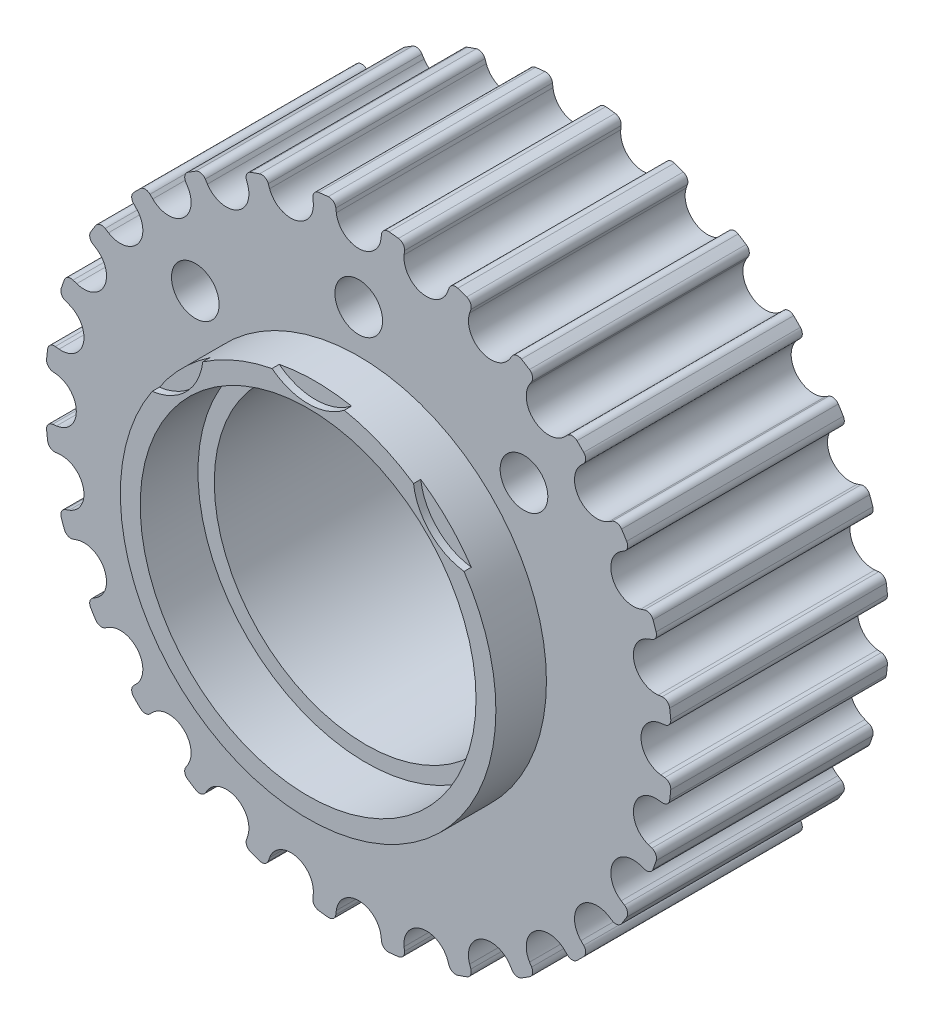
SolidWorks part; units mm, degrees
note: The reader was unsure of these and kept them because the rebuilt part matched: shared geometry of "草图15<2>".
ref_plane "前视基准面" through (0, 0, 0) normal (0, 0, 1) x (1, 0, 0)
ref_plane "上视基准面" through (0, 0, 0) normal (0, 1, 0) x (1, 0, 0)
ref_plane "右视基准面" through (0, 0, 0) normal (1, 0, 0) x (0, 0, -1)
sketch "草图2" plane through (0, 0, 0) normal (0, 0, 1) x (1, 0, 0)
  line L36 (1.3319, 20.7804) -> (1.2989, 20.5118)
  line L37 (-1.7978, 20.5118) -> (-1.8308, 20.7804)
  line L38 (-3.4222, 20.6011) -> (-3.3946, 20.3319)
  line L39 (-6.4137, 19.6428) -> (-6.5056, 19.8973)
  line L40 (-8.0172, 19.3684) -> (-7.9303, 19.1121)
  line L41 (-10.7204, 17.7684) -> (-10.8667, 17.9962)
  line L42 (-12.2227, 17.1441) -> (-12.081, 16.9135)
  line L43 (-14.5021, 14.9827) -> (-14.6954, 15.1722)
  line L44 (-15.8278, 14.0398) -> (-15.6383, 13.8465)
  line L45 (-17.5691, 11.4254) -> (-17.7997, 11.5671)
  line L46 (-18.6517, 10.2111) -> (-18.424, 10.0648)
  line L47 (-19.7676, 7.2748) -> (-20.024, 7.3616)
  line L48 (-20.5529, 5.85) -> (-20.2983, 5.7581)
  line L49 (-20.9874, 2.739) -> (-21.2567, 2.7666)
  line L50 (-21.436, 1.1752) -> (-21.1673, 1.1423)
  line L51 (-21.1673, -1.9545) -> (-21.436, -1.9875)
  line L52 (-21.2567, -3.5789) -> (-20.9874, -3.5512)
  line L53 (-20.2983, -6.5703) -> (-20.5529, -6.6623)
  line L54 (-20.024, -8.1739) -> (-19.7676, -8.087)
  line L55 (-18.424, -10.8771) -> (-18.6517, -11.0234)
  line L56 (-17.7997, -12.3793) -> (-17.5691, -12.2376)
  line L57 (-15.6383, -14.6588) -> (-15.8278, -14.8521)
  line L58 (-14.6954, -15.9845) -> (-14.5021, -15.795)
  line L59 (-12.081, -17.7258) -> (-12.2227, -17.9564)
  line L60 (-10.8667, -18.8084) -> (-10.7204, -18.5807)
  line L61 (-7.9303, -19.9243) -> (-8.0172, -20.1806)
  line L62 (-6.5056, -20.7096) -> (-6.4137, -20.455)
  line L63 (-3.3946, -21.1441) -> (-3.4222, -21.4133)
  line L64 (-1.8308, -21.5926) -> (-1.7978, -21.324)
  line L65 (1.2989, -21.324) -> (1.3319, -21.5926)
  line L66 (2.9233, -21.4133) -> (2.8957, -21.1441)
  line L67 (5.9148, -20.455) -> (6.0067, -20.7096)
  line L68 (7.5183, -20.1806) -> (7.4314, -19.9243)
  line L69 (10.2215, -18.5807) -> (10.3678, -18.8084)
  line L70 (11.7238, -17.9564) -> (11.5821, -17.7258)
  line L71 (14.0032, -15.795) -> (14.1965, -15.9845)
  line L72 (15.3289, -14.8521) -> (15.1394, -14.6588)
  line L73 (17.0702, -12.2376) -> (17.3008, -12.3793)
  line L74 (18.1528, -11.0234) -> (17.9251, -10.8771)
  line L75 (19.2687, -8.087) -> (19.5251, -8.1739)
  line L76 (20.054, -6.6623) -> (19.7994, -6.5703)
  line L77 (20.4885, -3.5512) -> (20.7578, -3.5789)
  line L78 (20.9371, -1.9875) -> (20.6684, -1.9545)
  line L79 (20.6684, 1.1423) -> (20.9371, 1.1752)
  line L80 (20.7578, 2.7666) -> (20.4885, 2.739)
  line L81 (19.7994, 5.7581) -> (20.054, 5.85)
  line L82 (19.5251, 7.3616) -> (19.2687, 7.2748)
  line L83 (17.9251, 10.0648) -> (18.1528, 10.2111)
  line L84 (17.3008, 11.5671) -> (17.0702, 11.4254)
  line L85 (15.1394, 13.8465) -> (15.3289, 14.0398)
  line L86 (14.1965, 15.1722) -> (14.0032, 14.9827)
  line L87 (11.5821, 16.9135) -> (11.7238, 17.1441)
  line L88 (10.3678, 17.9962) -> (10.2215, 17.7684)
  line L89 (7.4314, 19.1121) -> (7.5183, 19.3684)
  line L90 (6.0067, 19.8973) -> (5.9148, 19.6428)
  line L91 (2.8957, 20.3319) -> (2.9233, 20.6011)
  circle A72 centre (-0.2458, -0.3677) radius 12 construction
  circle A73 centre (-0.2458, -0.3677) radius 10.5
  arc A74 (2.9233, 20.6011) -> (2.5067, 21.1262) centre (2.4458, 20.6501) ccw
  arc A75 (2.5067, 21.1262) -> (1.8549, 21.1996) centre (-0.2495, -0.4061) ccw
  arc A76 (1.8549, 21.1996) -> (1.3319, 20.7804) centre (1.8083, 20.7219) ccw
  arc A77 (-1.7978, 20.5118) -> (1.2989, 20.5118) centre (-0.2495, 20.7019) ccw
  arc A78 (-1.8308, 20.7804) -> (-2.3538, 21.1996) centre (-2.3072, 20.7219) ccw
  arc A79 (-2.3538, 21.1996) -> (-3.0056, 21.1262) centre (-0.2495, -0.4061) ccw
  arc A80 (-3.0056, 21.1262) -> (-3.4222, 20.6011) centre (-2.9447, 20.6501) ccw
  arc A81 (-6.4137, 19.6428) -> (-3.3946, 20.3319) centre (-4.9464, 20.1727) ccw
  arc A82 (-6.5056, 19.8973) -> (-7.1087, 20.1897) centre (-6.9571, 19.7343) ccw
  arc A83 (-7.1087, 20.1897) -> (-7.7279, 19.973) centre (-0.2495, -0.4061) ccw
  arc A84 (-7.7279, 19.973) -> (-8.0172, 19.3684) centre (-7.5626, 19.5224) ccw
  arc A85 (-10.7204, 17.7684) -> (-7.9303, 19.1121) centre (-9.4079, 18.6115) ccw
  arc A86 (-10.8667, 17.9962) -> (-11.5198, 18.147) centre (-11.2706, 17.7367) ccw
  arc A87 (-11.5198, 18.147) -> (-12.0752, 17.798) centre (-0.2495, -0.4061) ccw
  arc A88 (-12.0752, 17.798) -> (-12.2227, 17.1441) centre (-11.8137, 17.3954) ccw
  arc A89 (-14.5021, 14.9827) -> (-12.081, 16.9135) centre (-13.4101, 16.0968) ccw
  arc A90 (-14.6954, 15.1722) -> (-15.3656, 15.1739) centre (-15.0314, 14.8294) ccw
  arc A91 (-15.3656, 15.1739) -> (-15.8295, 14.7101) centre (-0.2495, -0.4061) ccw
  arc A92 (-15.8295, 14.7101) -> (-15.8278, 14.0398) centre (-15.485, 14.3758) ccw
  arc A93 (-17.5691, 11.4254) -> (-15.6383, 13.8465) centre (-16.7524, 12.7545) ccw
  arc A94 (-17.7997, 11.5671) -> (-18.4535, 11.4196) centre (-18.051, 11.1582) ccw
  arc A95 (-18.4535, 11.4196) -> (-18.8026, 10.8642) centre (-0.2495, -0.4061) ccw
  arc A96 (-18.8026, 10.8642) -> (-18.6517, 10.2111) centre (-18.3923, 10.615) ccw
  arc A97 (-19.7676, 7.2748) -> (-18.424, 10.0648) centre (-19.2671, 8.7523) ccw
  arc A98 (-20.024, 7.3616) -> (-20.6286, 7.0724) centre (-20.178, 6.907) ccw
  arc A99 (-20.6286, 7.0724) -> (-20.8453, 6.4532) centre (-0.2495, -0.4061) ccw
  arc A100 (-20.8453, 6.4532) -> (-20.5529, 5.85) centre (-20.3899, 6.3015) ccw
  arc A101 (-20.9874, 2.739) -> (-20.2983, 5.7581) centre (-20.8282, 4.2909) ccw
  arc A102 (-21.2567, 2.7666) -> (-21.7818, 2.3501) centre (-21.3057, 2.2891) ccw
  arc A103 (-21.7818, 2.3501) -> (-21.8552, 1.6982) centre (-0.2495, -0.4061) ccw
  arc A104 (-21.8552, 1.6982) -> (-21.436, 1.1752) centre (-21.3775, 1.6517) ccw
  arc A105 (-21.1673, -1.9545) -> (-21.1673, 1.1423) centre (-21.3575, -0.4061) ccw
  arc A106 (-21.436, -1.9875) -> (-21.8552, -2.5104) centre (-21.3775, -2.4639) ccw
  arc A107 (-21.8552, -2.5104) -> (-21.7818, -3.1623) centre (-0.2495, -0.4061) ccw
  arc A108 (-21.7818, -3.1623) -> (-21.2567, -3.5789) centre (-21.3057, -3.1014) ccw
  arc A109 (-20.2983, -6.5703) -> (-20.9874, -3.5512) centre (-20.8282, -5.1031) ccw
  arc A110 (-20.5529, -6.6623) -> (-20.8453, -7.2654) centre (-20.3899, -7.1137) ccw
  arc A111 (-20.8453, -7.2654) -> (-20.6286, -7.8846) centre (-0.2495, -0.4061) ccw
  arc A112 (-20.6286, -7.8846) -> (-20.024, -8.1739) centre (-20.178, -7.7192) ccw
  arc A113 (-18.424, -10.8771) -> (-19.7676, -8.087) centre (-19.2671, -9.5645) ccw
  arc A114 (-18.6517, -11.0234) -> (-18.8026, -11.6764) centre (-18.3923, -11.4272) ccw
  arc A115 (-18.8026, -11.6764) -> (-18.4535, -12.2319) centre (-0.2495, -0.4061) ccw
  arc A116 (-18.4535, -12.2319) -> (-17.7997, -12.3793) centre (-18.051, -11.9704) ccw
  arc A117 (-15.6383, -14.6588) -> (-17.5691, -12.2376) centre (-16.7524, -13.5667) ccw
  arc A118 (-15.8278, -14.8521) -> (-15.8295, -15.5223) centre (-15.485, -15.1881) ccw
  arc A119 (-15.8295, -15.5223) -> (-15.3656, -15.9862) centre (-0.2495, -0.4061) ccw
  arc A120 (-15.3656, -15.9862) -> (-14.6954, -15.9845) centre (-15.0314, -15.6417) ccw
  arc A121 (-12.081, -17.7258) -> (-14.5021, -15.795) centre (-13.4101, -16.909) ccw
  arc A122 (-12.2227, -17.9564) -> (-12.0752, -18.6102) centre (-11.8137, -18.2077) ccw
  arc A123 (-12.0752, -18.6102) -> (-11.5198, -18.9592) centre (-0.2495, -0.4061) ccw
  arc A124 (-11.5198, -18.9592) -> (-10.8667, -18.8084) centre (-11.2706, -18.549) ccw
  arc A125 (-7.9303, -19.9243) -> (-10.7204, -18.5807) centre (-9.4079, -19.4238) ccw
  arc A126 (-8.0172, -20.1806) -> (-7.7279, -20.7853) centre (-7.5626, -20.3347) ccw
  arc A127 (-7.7279, -20.7853) -> (-7.1087, -21.0019) centre (-0.2495, -0.4061) ccw
  arc A128 (-7.1087, -21.0019) -> (-6.5056, -20.7096) centre (-6.9571, -20.5465) ccw
  arc A129 (-3.3946, -21.1441) -> (-6.4137, -20.455) centre (-4.9464, -20.9849) ccw
  arc A130 (-3.4222, -21.4133) -> (-3.0056, -21.9384) centre (-2.9447, -21.4623) ccw
  arc A131 (-3.0056, -21.9384) -> (-2.3538, -22.0119) centre (-0.2495, -0.4061) ccw
  arc A132 (-2.3538, -22.0119) -> (-1.8308, -21.5926) centre (-2.3072, -21.5341) ccw
  arc A133 (1.2989, -21.324) -> (-1.7978, -21.324) centre (-0.2495, -21.5141) ccw
  arc A134 (1.3319, -21.5926) -> (1.8549, -22.0119) centre (1.8083, -21.5341) ccw
  arc A135 (1.8549, -22.0119) -> (2.5067, -21.9384) centre (-0.2495, -0.4061) ccw
  arc A136 (2.5067, -21.9384) -> (2.9233, -21.4133) centre (2.4458, -21.4623) ccw
  arc A137 (5.9148, -20.455) -> (2.8957, -21.1441) centre (4.4475, -20.9849) ccw
  arc A138 (6.0067, -20.7096) -> (6.6098, -21.0019) centre (6.4582, -20.5465) ccw
  arc A139 (6.6098, -21.0019) -> (7.229, -20.7853) centre (-0.2495, -0.4061) ccw
  arc A140 (7.229, -20.7853) -> (7.5183, -20.1806) centre (7.0637, -20.3347) ccw
  arc A141 (10.2215, -18.5807) -> (7.4314, -19.9243) centre (8.909, -19.4238) ccw
  arc A142 (10.3678, -18.8084) -> (11.0209, -18.9592) centre (10.7716, -18.549) ccw
  arc A143 (11.0209, -18.9592) -> (11.5763, -18.6102) centre (-0.2495, -0.4061) ccw
  arc A144 (11.5763, -18.6102) -> (11.7238, -17.9564) centre (11.3148, -18.2077) ccw
  arc A145 (14.0032, -15.795) -> (11.5821, -17.7258) centre (12.9112, -16.909) ccw
  arc A146 (14.1965, -15.9845) -> (14.8667, -15.9862) centre (14.5325, -15.6417) ccw
  arc A147 (14.8667, -15.9862) -> (15.3306, -15.5223) centre (-0.2495, -0.4061) ccw
  arc A148 (15.3306, -15.5223) -> (15.3289, -14.8521) centre (14.9861, -15.1881) ccw
  arc A149 (17.0702, -12.2376) -> (15.1394, -14.6588) centre (16.2534, -13.5667) ccw
  arc A150 (17.3008, -12.3793) -> (17.9546, -12.2319) centre (17.5521, -11.9704) ccw
  arc A151 (17.9546, -12.2319) -> (18.3036, -11.6764) centre (-0.2495, -0.4061) ccw
  arc A152 (18.3036, -11.6764) -> (18.1528, -11.0234) centre (17.8934, -11.4272) ccw
  arc A153 (19.2687, -8.087) -> (17.9251, -10.8771) centre (18.7682, -9.5645) ccw
  arc A154 (19.5251, -8.1739) -> (20.1297, -7.8846) centre (19.6791, -7.7192) ccw
  arc A155 (20.1297, -7.8846) -> (20.3464, -7.2654) centre (-0.2495, -0.4061) ccw
  arc A156 (20.3464, -7.2654) -> (20.054, -6.6623) centre (19.891, -7.1137) ccw
  arc A157 (20.4885, -3.5512) -> (19.7994, -6.5703) centre (20.3293, -5.1031) ccw
  arc A158 (20.7578, -3.5789) -> (21.2829, -3.1623) centre (20.8067, -3.1014) ccw
  arc A159 (21.2829, -3.1623) -> (21.3563, -2.5104) centre (-0.2495, -0.4061) ccw
  arc A160 (21.3563, -2.5104) -> (20.9371, -1.9875) centre (20.8786, -2.4639) ccw
  arc A161 (20.6684, 1.1423) -> (20.6684, -1.9545) centre (20.8585, -0.4061) ccw
  arc A162 (20.9371, 1.1752) -> (21.3563, 1.6982) centre (20.8786, 1.6517) ccw
  arc A163 (21.3563, 1.6982) -> (21.2829, 2.3501) centre (-0.2495, -0.4061) ccw
  arc A164 (21.2829, 2.3501) -> (20.7578, 2.7666) centre (20.8067, 2.2891) ccw
  arc A165 (19.7994, 5.7581) -> (20.4885, 2.739) centre (20.3293, 4.2909) ccw
  arc A166 (20.054, 5.85) -> (20.3464, 6.4532) centre (19.891, 6.3015) ccw
  arc A167 (20.3464, 6.4532) -> (20.1297, 7.0724) centre (-0.2495, -0.4061) ccw
  arc A168 (20.1297, 7.0724) -> (19.5251, 7.3616) centre (19.6791, 6.907) ccw
  arc A169 (17.9251, 10.0648) -> (19.2687, 7.2748) centre (18.7682, 8.7523) ccw
  arc A170 (18.1528, 10.2111) -> (18.3036, 10.8642) centre (17.8934, 10.615) ccw
  arc A171 (18.3036, 10.8642) -> (17.9546, 11.4196) centre (-0.2495, -0.4061) ccw
  arc A172 (17.9546, 11.4196) -> (17.3008, 11.5671) centre (17.5521, 11.1582) ccw
  arc A173 (15.1394, 13.8465) -> (17.0702, 11.4254) centre (16.2534, 12.7545) ccw
  arc A174 (15.3289, 14.0398) -> (15.3306, 14.7101) centre (14.9861, 14.3758) ccw
  arc A175 (15.3306, 14.7101) -> (14.8667, 15.1739) centre (-0.2495, -0.4061) ccw
  arc A176 (14.8667, 15.1739) -> (14.1965, 15.1722) centre (14.5325, 14.8294) ccw
  arc A177 (11.5821, 16.9135) -> (14.0032, 14.9827) centre (12.9112, 16.0968) ccw
  arc A178 (11.7238, 17.1441) -> (11.5763, 17.798) centre (11.3148, 17.3954) ccw
  arc A179 (11.5763, 17.798) -> (11.0209, 18.147) centre (-0.2495, -0.4061) ccw
  arc A180 (11.0209, 18.147) -> (10.3678, 17.9962) centre (10.7716, 17.7367) ccw
  arc A181 (7.4314, 19.1121) -> (10.2215, 17.7684) centre (8.909, 18.6115) ccw
  arc A182 (7.5183, 19.3684) -> (7.229, 19.973) centre (7.0637, 19.5224) ccw
  arc A183 (7.229, 19.973) -> (6.6098, 20.1897) centre (-0.2495, -0.4061) ccw
  arc A184 (6.6098, 20.1897) -> (6.0067, 19.8973) centre (6.4582, 19.7343) ccw
  arc A185 (2.8957, 20.3319) -> (5.9148, 19.6428) centre (4.4475, 20.1727) ccw
extrude "凸台-拉伸1" add sketch "草图2" along normal blind 15
move or copy body "实体-移动/复制1" bodies to move or copy 106 copy no translate (-21.7751, 0, 0)
sketch "草图12" plane through (0, 0, 15) normal (0, 0, 1) x (1, 0, 0)
  circle A0 centre (-22.0209, -0.3677) radius 10.5 construction
  circle A1 centre (-22.0209, -0.3677) radius 10.5
  circle A2 centre (-22.0246, -0.3096) radius 11.625
  circle A3 centre (-22.0246, -0.3096) radius 13
  circle A4 centre (-22.0209, -0.3677) radius 16
  point P7 (-6.0209, -0.3677)
  point P10 (-10.7072, -11.6815)
  point P11 (-22.0209, -16.3677)
  point P12 (-33.3346, -11.6815)
  point P13 (-38.0209, -0.3677)
  point P14 (-33.3346, 10.946)
  point P15 (-22.0209, 15.6323)
  point P16 (-10.7072, 10.946)
  point P17 (-22.0209, -0.3677)
  dimension "D1" = 23.25
  dimension "D2" = 26
  dimension "D3" = 32
  dimension "D4" = 8
extrude "凸台-拉伸2" add sketch "草图12" along normal blind 3.5 and the other way blind 19.5 contours A3 A2
hole_wizard "M4 螺纹孔1" positions "3D草图1" profile "草图13" tap size "M4" standard "GB" end condition through all
sketch3d "3D草图1"
  circle A0 centre (-22.0209, -0.3677, 15) radius 16 construction
  point P0 (-33.3346, 10.946, 15)
  point P3 (-22.0209, 15.6323, 15)
  point P6 (-10.5793, 10.8166, 15)
  point P10 (-22.0209, -0.3677, 31)
cosmetic thread "孔螺蚊线4" parameters "D2"=4
cosmetic thread "孔螺蚊线5" parameters "D2"=4
cosmetic thread "孔螺蚊线6" parameters "D2"=4
sketch "草图13" plane through (-33.3346, 10.946, 15) normal (1, 0, 0) x (0, -1, 0)
  line L0 (0, 0) -> (0, 19.5)
  line L1 (0, 19.5) -> (1.65, 19.5)
  line L2 (1.65, 19.5) -> (1.65, 0)
  line L5 (1.65, 0) -> (0, 0)
  line L11 (0, -6.35) -> (0, 107.95) construction
  dimension "通孔螺纹孔钻头直径" = 3.3
  dimension "通孔螺纹孔钻头深度" = 19.5
sketch "草图14" plane through (0, 0, 15) normal (0, 0, 1) x (1, 0, 0)
  circle A0 centre (-22.0209, -0.3677) radius 10.5 construction
  circle A1 centre (-22.0246, -0.3096) radius 11.625
  circle A2 centre (-22.0246, -0.3096) radius 11.625
  circle A3 centre (-22.0209, -0.3677) radius 10.5
  dimension "D1" = 0
extrude "切除-拉伸1" cut sketch "草图14" against normal blind 0.5
sketch "草图15" plane through (0, 0, 15) normal (0, 0, 1) x (1, 0, 0)
  circle A0 centre (-22.0209, -0.3677) radius 16 construction
  circle A1 centre (-22.0209, -0.3677) radius 16 construction
  circle A2 centre (-22.0209, 15.6323) radius 4.05
  circle A3 centre (-10.7072, 10.946) radius 4.05
  circle A4 centre (-6.0209, -0.3677) radius 4.05 [skipped]
  circle A8 centre (-38.0209, -0.3677) radius 4.05 [skipped]
  circle A9 centre (-33.3346, 10.946) radius 4.05
  circle A10 centre (-10.7072, -11.6815) radius 4.05 [skipped]
  circle A11 centre (-33.3346, -11.6815) radius 4.05 [skipped]
  circle A12 centre (-22.0209, -16.3677) radius 4.05 [skipped]
  point P0 (-33.3346, -11.6815)
  point P2 (-22.0209, -16.3677)
  point P4 (-10.7072, -11.6815)
  point P6 (-10.7072, 10.946)
  point P8 (-22.0209, 15.6323)
  point P10 (-33.3346, 10.946)
  point P34 (-22.0209, -0.3677)
  dimension "D1" = 8.1
  dimension "D2" = 8
extrude "切除-拉伸2" cut sketch "草图15" against normal blind 0.5 from surface at 3.5 starting at face at (-10.3996, -0.3096, 18.5)
extrude "切除-拉伸3" cut sketch "草图15<2>" along normal blind 1.5 from surface at -19.5
sketch "草图15<2>" plane through (0, 0, 15) normal (0, 0, 1) x (1, 0, 0) same geometry as "草图15"
sketch "草图16" plane through (0, 0, 0) normal (0, 0, -1) x (-1, 0, 0)
  circle A0 centre (22.0209, -0.3677) radius 10.5 construction
  circle A1 centre (22.0246, -0.3096) radius 11.625
  circle A2 centre (22.0246, -0.3096) radius 11.625
  circle A3 centre (22.0209, -0.3677) radius 10.5
  dimension "D1" = 0
extrude "凸台-拉伸3" add sketch "草图16" along normal blind 0.5
